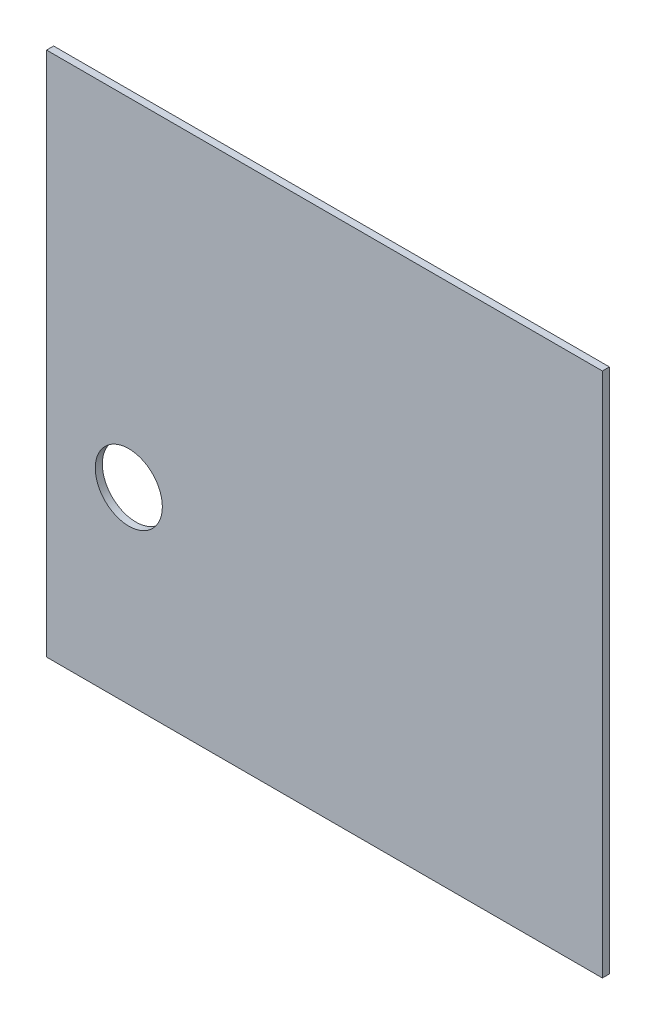
SolidWorks part; units mm, degrees
ref_plane "Front Plane" through (0, 0, 0) normal (0, 0, 1) x (1, 0, 0)
ref_plane "Top Plane" through (0, 0, 0) normal (0, 1, 0) x (1, 0, 0)
ref_plane "Right Plane" through (0, 0, 0) normal (1, 0, 0) x (0, 0, -1)
sketch "Sketch1" plane through (0, 0, 0) normal (0, 0, 1) x (1, 0, 0)
  line L1 (0, 0) -> (236.55, 0)
  line L2 (0, 0) -> (0, 223.74)
  line L3 (0, 223.74) -> (236.55, 223.74)
  line L4 (236.55, 0) -> (236.55, 223.74)
  dimension "D1" = 236.55
  dimension "D2" = 223.74
extrude "Boss-Extrude1" add sketch "Sketch1" along normal blind 3
sketch "Sketch2" plane through (0, 0, 3) normal (0, 0, 1) x (1, 0, 0)
  line L0 (236.55, 223.74) -> (0, 223.74) construction
  line L2 (0, 223.74) -> (0, 0) construction
  circle A0 centre (35, 80.05) radius 14.275
  dimension "D1" = 28.55
  dimension "D2" = 35
  dimension "D3" = 143.69
extrude "Cut-Extrude1" cut sketch "Sketch2" against normal blind 3
